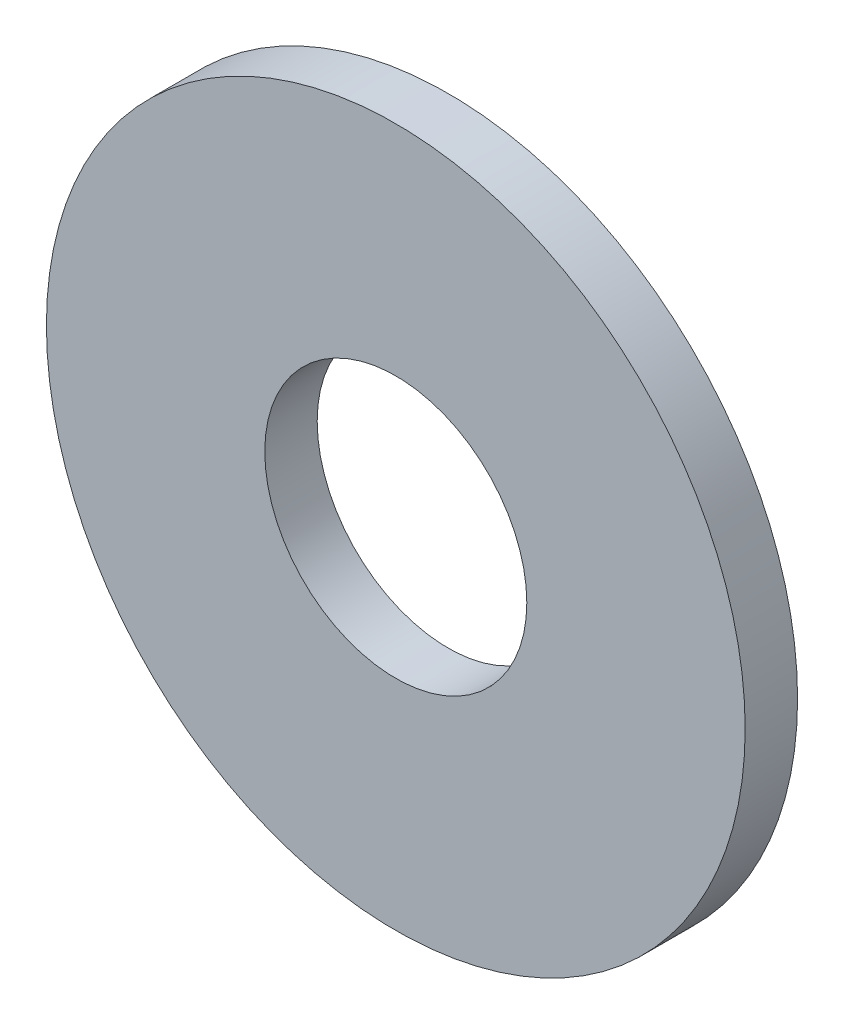
SolidWorks part; units mm, degrees
ref_plane "Спереди" through (0, 0, 0) normal (0, 0, 1) x (1, 0, 0)
ref_plane "Сверху" through (0, 0, 0) normal (0, 1, 0) x (1, 0, 0)
ref_plane "Справа" through (0, 0, 0) normal (1, 0, 0) x (0, 0, -1)
sketch "Эскиз1" plane through (0, 0, 0) normal (0, 0, 1) x (1, 0, 0)
  circle A0 centre (0, 0) radius 2
  dimension "d2" = 4
extrude "Основание-Вытянуть" add sketch "Эскиз1" along normal blind 0.3
sketch "Эскиз2" plane through (0, 0, 0.3) normal (0, 0, 1) x (1, 0, 0)
  circle A0 centre (0, 0) radius 0.75
  dimension "d1" = 1.5
extrude "Вырез-Вытянуть1" cut sketch "Эскиз2" against normal through all
chamfer "Фаска1" [suppressed] distance 0.12 angle 45
